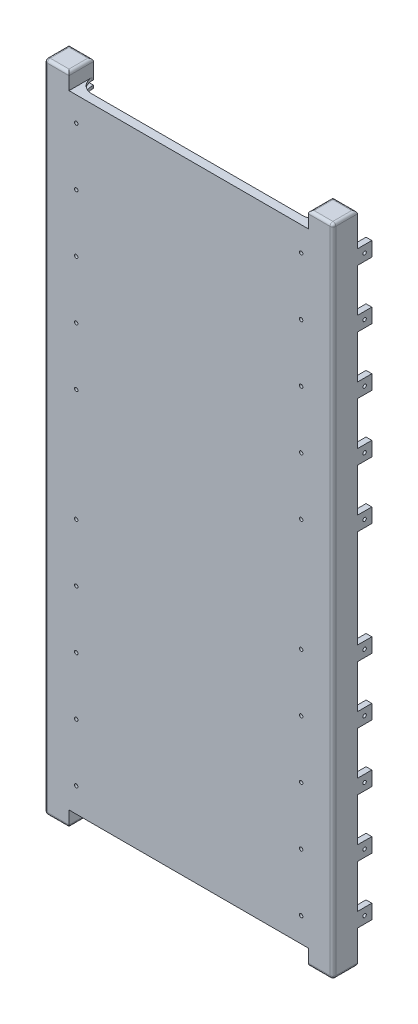
SolidWorks part; units mm, degrees
ref_plane "Front Plane" through (0, 0, 0) normal (0, 0, 1) x (1, 0, 0)
ref_plane "Top Plane" through (0, 0, 0) normal (0, 1, 0) x (1, 0, 0)
ref_plane "Right Plane" through (0, 0, 0) normal (1, 0, 0) x (0, 0, -1)
sketch "Sketch1" plane through (0, 0, 0) normal (0, 1, 0) x (1, 0, 0)
  line L1 (-3.25, -4.25) -> (4.25, -4.25)
  line L2 (-4.25, -3.25) -> (-4.25, 4.25)
  line L3 (-4.25, 4.25) -> (4.25, 4.25)
  line L4 (4.25, -4.25) -> (4.25, 4.25)
  line L5 (-4.25, -4.25) -> (4.25, 4.25) construction
  line L6 (-4.25, 4.25) -> (4.25, -4.25) construction
  arc A0 (-3.25, -4.25) -> (-4.25, -3.25) centre (-3.25, -3.25) cw
  point P0 (0, 0)
  dimension "D2" = 1
  dimension "D1" = 8.5
extrude "Boss-Extrude1" add sketch "Sketch1" along normal blind 227
ref_plane "Plane2" through (45.75, 0, 0) normal (-1, 0, 0) x (0, 0, 1)
ref_plane "Plane3" through (0, 113.5, 0) normal (0, 1, 0) x (1, 0, 0)
fillet "Fillet1" radius 1 10 edges at (0, 0, -4.25) (-4.25, 0, -0.5) (-3.9571, 0, 3.9571) (0.5, 0, 4.25) (4.25, 0, 0) (0.5, 227, 4.25) (-3.9571, 227, 3.9571) (-4.25, 227, -0.5) (0, 227, -4.25) (4.25, 227, 0)
ref_plane "Plane1" through (0, 0, 0) normal (-0.7071, 0, -0.7071) x (-0.7071, 0, 0.7071)
sketch "Sketch2" plane through (4.25, 0, 0) normal (1, 0, 0) x (0, 0, -1)
  line L0 (-4.25, 226) -> (-4.25, 1) construction
  line L1 (-4.25, 215.5) -> (-2.25, 215.5)
  line L2 (-4.25, 215.5) -> (-4.25, 210.5)
  line L3 (-4.25, 210.5) -> (-2.25, 210.5)
  line L4 (-2.25, 215.5) -> (-2.25, 210.5)
  line L5 (-3.25, 227) -> (3.25, 227) construction
  line L6 (-4.25, 195.5) -> (-2.25, 195.5)
  line L8 (-4.25, 195.5) -> (-4.25, 190.5)
  line L9 (-4.25, 190.5) -> (-2.25, 190.5)
  line L10 (-2.25, 195.5) -> (-2.25, 190.5)
  line L11 (-4.25, 175.5) -> (-2.25, 175.5)
  line L12 (-4.25, 175.5) -> (-4.25, 170.5)
  line L13 (-4.25, 170.5) -> (-2.25, 170.5)
  line L14 (-2.25, 175.5) -> (-2.25, 170.5)
  line L15 (-4.25, 155.5) -> (-2.25, 155.5)
  line L16 (-4.25, 155.5) -> (-4.25, 150.5)
  line L17 (-4.25, 150.5) -> (-2.25, 150.5)
  line L18 (-2.25, 155.5) -> (-2.25, 150.5)
  line L19 (-4.25, 135.5) -> (-2.25, 135.5)
  line L20 (-4.25, 135.5) -> (-4.25, 130.5)
  line L21 (-4.25, 130.5) -> (-2.25, 130.5)
  line L22 (-2.25, 135.5) -> (-2.25, 130.5)
  line L27 (-4.25, 120.5) -> (4.25, 120.5) construction
  line L28 (4.25, 226) -> (4.25, 1) construction
  line L29 (-4.25, 220.5) -> (4.25, 220.5) construction
  line L30 (-4.25, 113.5) -> (4.25, 113.5) construction
  line L35 (-2.25, 91.5) -> (-2.25, 96.5)
  line L36 (-4.25, 96.5) -> (-2.25, 96.5)
  line L37 (-4.25, 91.5) -> (-4.25, 96.5)
  line L38 (-4.25, 91.5) -> (-2.25, 91.5)
  line L39 (-2.25, 71.5) -> (-2.25, 76.5)
  line L40 (-4.25, 76.5) -> (-2.25, 76.5)
  line L41 (-4.25, 71.5) -> (-4.25, 76.5)
  line L42 (-4.25, 71.5) -> (-2.25, 71.5)
  line L43 (-2.25, 51.5) -> (-2.25, 56.5)
  line L44 (-4.25, 56.5) -> (-2.25, 56.5)
  line L45 (-4.25, 51.5) -> (-4.25, 56.5)
  line L46 (-4.25, 51.5) -> (-2.25, 51.5)
  line L47 (-2.25, 31.5) -> (-2.25, 36.5)
  line L48 (-4.25, 36.5) -> (-2.25, 36.5)
  line L49 (-4.25, 31.5) -> (-4.25, 36.5)
  line L50 (-4.25, 31.5) -> (-2.25, 31.5)
  line L51 (-2.25, 11.5) -> (-2.25, 16.5)
  line L52 (-4.25, 16.5) -> (-2.25, 16.5)
  line L53 (-4.25, 11.5) -> (-4.25, 16.5)
  line L54 (-4.25, 11.5) -> (-2.25, 11.5)
  line L55 (-4.25, 115.5) -> (-2.25, 115.5)
  line L56 (-4.25, 115.5) -> (-4.25, 110.5)
  line L57 (-2.25, 115.5) -> (-2.25, 110.5)
  line L58 (-4.25, 110.5) -> (-2.25, 110.5)
  dimension "D1" = 2
  dimension "D2" = 100
  dimension "D3" = 5
  dimension "D4" = 6
  dimension "D5" = 20
  dimension "D6" = 6.5
  dimension "D7" = 5
extrude "Boss-Extrude2" add sketch "Sketch2" along normal blind 5
sketch "Sketch13" plane through (4.25, 0, 0) normal (-1, 0, 0) x (0, 0, 1)
  line L1 (4.25, 220.5) -> (4.05, 220.5)
  line L2 (4.25, 220.5) -> (4.25, 6.5)
  line L3 (4.25, 6.5) -> (4.05, 6.5)
  line L4 (4.05, 220.5) -> (4.05, 6.5)
  line L6 (3.25, 227) -> (-3.25, 227) construction
  line L7 (-3.25, 0) -> (3.25, 0) construction
  dimension "D1" = 0.2
  dimension "D2" = 6.5
  dimension "D3" = 6.5
extrude "Boss-Extrude6" add sketch "Sketch13" along normal up to surface (41.5 mm away)
hole_wizard "#0-80 Tapped Hole1" positions "Sketch12" profile "Sketch11" tap size "#0-80" standard "ANSI Inch"
sketch "Sketch12" plane through (0, 0, 4.25) normal (0, 0, 1) x (1, 0, 0)
  line L0 (9.25, 215.5) -> (4.25, 215.5) construction
  line L2 (9.25, 215.5) -> (9.25, 210.5) construction
  line L5 (4.25, 113.5) -> (-3.25, 113.5) construction
  line L7 (-3.25, 226) -> (-3.25, 1) construction
  line L8 (4.25, 130.5) -> (4.25, 96.5) construction
  point P0 (6.75, 213)
  point P23 (6.75, 193)
  point P24 (6.75, 173)
  point P25 (6.75, 153)
  point P26 (6.75, 133)
  point P40 (6.75, 94)
  point P41 (6.75, 74)
  point P42 (6.75, 54)
  point P43 (6.75, 34)
  point P44 (6.75, 14)
  dimension "D1" = 2.5
  dimension "D2" = 2.5
  dimension "D4" = 20
  dimension "D3" = 5
sketch "Sketch11" plane through (6.75, 213, 4.25) normal (1, 0, 0) x (0, -1, 0)
  line L0 (0, 0) -> (0, 4.3584)
  line L1 (0, 4.3584) -> (0.5956, 4.0005)
  line L2 (0.5956, 4.0005) -> (0.5956, 0)
  line L5 (0.5956, 0) -> (0, 0)
  line L10 (0, 4.3584) -> (-0.5956, 4.0005) construction
  line L11 (0, -6.35) -> (0, 107.95) construction
  dimension "Tap Drill Dia." = 1.1913
  dimension "Tap Drill Depth" = 4.0005
  dimension "Drill Angle" = 118
cosmetic thread "Hole Thread1" parameters "D1"=2, "D2"=1.524
cosmetic thread "Hole Thread2" parameters "D1"=2, "D2"=1.524
cosmetic thread "Hole Thread11" parameters "D1"=2, "D2"=1.524
cosmetic thread "Hole Thread12" parameters "D1"=2, "D2"=1.524
cosmetic thread "Hole Thread13" parameters "D1"=2, "D2"=1.524
cosmetic thread "Hole Thread14" parameters "D1"=2, "D2"=1.524
cosmetic thread "Hole Thread15" parameters "D1"=2, "D2"=1.524
cosmetic thread "Hole Thread16" parameters "D1"=2, "D2"=1.524
cosmetic thread "Hole Thread17" parameters "D1"=2, "D2"=1.524
cosmetic thread "Hole Thread18" parameters "D1"=2, "D2"=1.524
fillet "Fillet2" radius 2.5 20 edges at (9.25, 215.5, 3.15) (9.25, 195.5, 3.15) (9.25, 175.5, 3.15) (9.25, 155.5, 3.15) (9.25, 135.5, 3.15) (9.25, 91.5, 3.15) (9.25, 71.5, 3.15) (9.25, 51.5, 3.15) (9.25, 31.5, 3.15) (9.25, 11.5, 3.15) (4.25, 215.5, 3.15) (4.25, 195.5, 3.15) (4.25, 175.5, 3.15) (4.25, 155.5, 3.15) (4.25, 135.5, 3.15) (4.25, 91.5, 3.15) (4.25, 71.5, 3.15) (4.25, 51.5, 3.15) (4.25, 11.5, 3.15) (4.25, 31.5, 3.15)
mirror "Mirror1" about plane through (0, 0, 0) normal (-0.7071, 0, -0.7071) of "#0-80 Tapped Hole1", "Boss-Extrude2"
sketch "Sketch3" plane through (0, 227, 0) normal (0, 1, 0) x (1, 0, 0)
  line L1 (-2.25, -2.25) -> (4.25, -2.25)
  line L2 (-2.25, -2.25) -> (-2.25, 4.25)
  line L3 (-2.25, 4.25) -> (4.25, 4.25)
  line L4 (4.25, -2.25) -> (4.25, 4.25)
  line L6 (4.25, -4.25) -> (-3.25, -4.25) construction
  line L7 (-4.25, -3.25) -> (-4.25, 4.25) construction
  dimension "D1" = 2
  dimension "D2" = 2
extrude "Cut-Extrude1" cut sketch "Sketch3" against normal offset from surface (214 mm away) 6.5 from offset 6.5 up to face at (0, 0, 0) offset against normal yes
mirror "Mirror7" about plane through (45.75, 0, 0) normal (-1, 0, 0) of "Fillet2", "Boss-Extrude1", "Fillet1", "Boss-Extrude2", "Boss-Extrude6", "#0-80 Tapped Hole1", "Mirror1", "Cut-Extrude1"
sketch "Sketch14" plane through (-2.25, 0, 0) normal (1, 0, 0) x (0, 0, -1)
  line L0 (-2.25, 6.5) -> (-2.25, 220.5) construction
  line L1 (-4.25, 8.1) -> (4.25, 8.1)
  line L2 (-4.25, 8.1) -> (-4.25, 9.1)
  line L3 (-4.25, 9.1) -> (4.25, 9.1)
  line L4 (4.25, 8.1) -> (4.25, 9.1)
  line L5 (4.25, 6.5) -> (4.25, 11.5) construction
  line L6 (4.25, 6.5) -> (-2.25, 6.5) construction
  line L7 (-4.25, 18.1) -> (4.25, 18.1)
  line L8 (-4.25, 6.5) -> (4.25, 6.5)
  line L9 (-4.25, 6.5) -> (-4.25, 5.5)
  line L10 (-4.25, 5.5) -> (4.25, 5.5)
  line L11 (4.25, 6.5) -> (4.25, 5.5)
  line L12 (-4.25, 18.1) -> (-4.25, 19.1)
  line L13 (-4.25, 19.1) -> (4.25, 19.1)
  line L14 (4.25, 18.1) -> (4.25, 19.1)
  line L15 (-4.25, 16.5) -> (4.25, 16.5)
  line L16 (-4.25, 16.5) -> (-4.25, 15.5)
  line L17 (-4.25, 15.5) -> (4.25, 15.5)
  line L18 (4.25, 16.5) -> (4.25, 15.5)
  line L19 (-4.25, 28.1) -> (4.25, 28.1)
  line L20 (-4.25, 28.1) -> (-4.25, 29.1)
  line L21 (-4.25, 29.1) -> (4.25, 29.1)
  line L22 (4.25, 28.1) -> (4.25, 29.1)
  line L23 (-4.25, 26.5) -> (4.25, 26.5)
  line L24 (-4.25, 26.5) -> (-4.25, 25.5)
  line L25 (-4.25, 25.5) -> (4.25, 25.5)
  line L26 (4.25, 26.5) -> (4.25, 25.5)
  line L27 (-4.25, 38.1) -> (4.25, 38.1)
  line L28 (-4.25, 38.1) -> (-4.25, 39.1)
  line L29 (-4.25, 39.1) -> (4.25, 39.1)
  line L30 (4.25, 38.1) -> (4.25, 39.1)
  line L31 (-4.25, 36.5) -> (4.25, 36.5)
  line L32 (-4.25, 36.5) -> (-4.25, 35.5)
  line L33 (-4.25, 35.5) -> (4.25, 35.5)
  line L34 (4.25, 36.5) -> (4.25, 35.5)
  line L35 (-4.25, 48.1) -> (4.25, 48.1)
  line L36 (-4.25, 48.1) -> (-4.25, 49.1)
  line L37 (-4.25, 49.1) -> (4.25, 49.1)
  line L38 (4.25, 48.1) -> (4.25, 49.1)
  line L39 (-4.25, 46.5) -> (4.25, 46.5)
  line L40 (-4.25, 46.5) -> (-4.25, 45.5)
  line L41 (-4.25, 45.5) -> (4.25, 45.5)
  line L42 (4.25, 46.5) -> (4.25, 45.5)
  line L43 (-4.25, 58.1) -> (4.25, 58.1)
  line L44 (-4.25, 58.1) -> (-4.25, 59.1)
  line L45 (-4.25, 59.1) -> (4.25, 59.1)
  line L46 (4.25, 58.1) -> (4.25, 59.1)
  line L47 (-4.25, 56.5) -> (4.25, 56.5)
  line L48 (-4.25, 56.5) -> (-4.25, 55.5)
  line L49 (-4.25, 55.5) -> (4.25, 55.5)
  line L50 (4.25, 56.5) -> (4.25, 55.5)
  line L51 (-4.25, 68.1) -> (4.25, 68.1)
  line L52 (-4.25, 68.1) -> (-4.25, 69.1)
  line L53 (-4.25, 69.1) -> (4.25, 69.1)
  line L54 (4.25, 68.1) -> (4.25, 69.1)
  line L55 (-4.25, 66.5) -> (4.25, 66.5)
  line L56 (-4.25, 66.5) -> (-4.25, 65.5)
  line L57 (-4.25, 65.5) -> (4.25, 65.5)
  line L58 (4.25, 66.5) -> (4.25, 65.5)
  line L59 (-4.25, 78.1) -> (4.25, 78.1)
  line L60 (-4.25, 78.1) -> (-4.25, 79.1)
  line L61 (-4.25, 79.1) -> (4.25, 79.1)
  line L62 (4.25, 78.1) -> (4.25, 79.1)
  line L63 (-4.25, 76.5) -> (4.25, 76.5)
  line L64 (-4.25, 76.5) -> (-4.25, 75.5)
  line L65 (-4.25, 75.5) -> (4.25, 75.5)
  line L66 (4.25, 76.5) -> (4.25, 75.5)
  line L67 (-4.25, 88.1) -> (4.25, 88.1)
  line L68 (-4.25, 88.1) -> (-4.25, 89.1)
  line L69 (-4.25, 89.1) -> (4.25, 89.1)
  line L70 (4.25, 88.1) -> (4.25, 89.1)
  line L71 (-4.25, 86.5) -> (4.25, 86.5)
  line L72 (-4.25, 86.5) -> (-4.25, 85.5)
  line L73 (-4.25, 85.5) -> (4.25, 85.5)
  line L74 (4.25, 86.5) -> (4.25, 85.5)
  line L75 (-4.25, 98.1) -> (4.25, 98.1)
  line L76 (-4.25, 98.1) -> (-4.25, 99.1)
  line L77 (-4.25, 99.1) -> (4.25, 99.1)
  line L78 (4.25, 98.1) -> (4.25, 99.1)
  line L79 (-4.25, 96.5) -> (4.25, 96.5)
  line L80 (-4.25, 96.5) -> (-4.25, 95.5)
  line L81 (-4.25, 95.5) -> (4.25, 95.5)
  line L82 (4.25, 96.5) -> (4.25, 95.5)
  line L83 (-4.25, 108.1) -> (4.25, 108.1)
  line L84 (-4.25, 108.1) -> (-4.25, 109.1)
  line L85 (-4.25, 109.1) -> (4.25, 109.1)
  line L86 (4.25, 108.1) -> (4.25, 109.1)
  line L87 (-4.25, 106.5) -> (4.25, 106.5)
  line L88 (-4.25, 106.5) -> (-4.25, 105.5)
  line L89 (-4.25, 105.5) -> (4.25, 105.5)
  line L90 (4.25, 106.5) -> (4.25, 105.5)
  line L91 (4.25, 96.5) -> (4.25, 130.5) construction
  line L92 (4.25, 113.5) -> (-2.25, 113.5) construction
  line L93 (4.25, 120.5) -> (4.25, 121.5)
  line L94 (-4.25, 121.5) -> (4.25, 121.5)
  line L95 (-4.25, 120.5) -> (-4.25, 121.5)
  line L96 (-4.25, 120.5) -> (4.25, 120.5)
  line L97 (4.25, 118.9) -> (4.25, 117.9)
  line L98 (-4.25, 117.9) -> (4.25, 117.9)
  line L99 (-4.25, 118.9) -> (-4.25, 117.9)
  line L100 (-4.25, 118.9) -> (4.25, 118.9)
  line L101 (4.25, 130.5) -> (4.25, 131.5)
  line L102 (-4.25, 131.5) -> (4.25, 131.5)
  line L103 (-4.25, 130.5) -> (-4.25, 131.5)
  line L104 (-4.25, 130.5) -> (4.25, 130.5)
  line L105 (4.25, 128.9) -> (4.25, 127.9)
  line L106 (-4.25, 127.9) -> (4.25, 127.9)
  line L107 (-4.25, 128.9) -> (-4.25, 127.9)
  line L108 (-4.25, 128.9) -> (4.25, 128.9)
  line L109 (4.25, 140.5) -> (4.25, 141.5)
  line L110 (-4.25, 141.5) -> (4.25, 141.5)
  line L111 (-4.25, 140.5) -> (-4.25, 141.5)
  line L112 (-4.25, 140.5) -> (4.25, 140.5)
  line L113 (4.25, 138.9) -> (4.25, 137.9)
  line L114 (-4.25, 137.9) -> (4.25, 137.9)
  line L115 (-4.25, 138.9) -> (-4.25, 137.9)
  line L116 (-4.25, 138.9) -> (4.25, 138.9)
  line L117 (4.25, 150.5) -> (4.25, 151.5)
  line L118 (-4.25, 151.5) -> (4.25, 151.5)
  line L119 (-4.25, 150.5) -> (-4.25, 151.5)
  line L120 (-4.25, 150.5) -> (4.25, 150.5)
  line L121 (4.25, 148.9) -> (4.25, 147.9)
  line L122 (-4.25, 147.9) -> (4.25, 147.9)
  line L123 (-4.25, 148.9) -> (-4.25, 147.9)
  line L124 (-4.25, 148.9) -> (4.25, 148.9)
  line L125 (4.25, 160.5) -> (4.25, 161.5)
  line L126 (-4.25, 161.5) -> (4.25, 161.5)
  line L127 (-4.25, 160.5) -> (-4.25, 161.5)
  line L128 (-4.25, 160.5) -> (4.25, 160.5)
  line L129 (4.25, 158.9) -> (4.25, 157.9)
  line L130 (-4.25, 157.9) -> (4.25, 157.9)
  line L131 (-4.25, 158.9) -> (-4.25, 157.9)
  line L132 (-4.25, 158.9) -> (4.25, 158.9)
  line L133 (4.25, 170.5) -> (4.25, 171.5)
  line L134 (-4.25, 171.5) -> (4.25, 171.5)
  line L135 (-4.25, 170.5) -> (-4.25, 171.5)
  line L136 (-4.25, 170.5) -> (4.25, 170.5)
  line L137 (4.25, 168.9) -> (4.25, 167.9)
  line L138 (-4.25, 167.9) -> (4.25, 167.9)
  line L139 (-4.25, 168.9) -> (-4.25, 167.9)
  line L140 (-4.25, 168.9) -> (4.25, 168.9)
  line L141 (4.25, 180.5) -> (4.25, 181.5)
  line L142 (-4.25, 181.5) -> (4.25, 181.5)
  line L143 (-4.25, 180.5) -> (-4.25, 181.5)
  line L144 (-4.25, 180.5) -> (4.25, 180.5)
  line L145 (4.25, 178.9) -> (4.25, 177.9)
  line L146 (-4.25, 177.9) -> (4.25, 177.9)
  line L147 (-4.25, 178.9) -> (-4.25, 177.9)
  line L148 (-4.25, 178.9) -> (4.25, 178.9)
  line L149 (4.25, 190.5) -> (4.25, 191.5)
  line L150 (-4.25, 191.5) -> (4.25, 191.5)
  line L151 (-4.25, 190.5) -> (-4.25, 191.5)
  line L152 (-4.25, 190.5) -> (4.25, 190.5)
  line L153 (4.25, 188.9) -> (4.25, 187.9)
  line L154 (-4.25, 187.9) -> (4.25, 187.9)
  line L155 (-4.25, 188.9) -> (-4.25, 187.9)
  line L156 (-4.25, 188.9) -> (4.25, 188.9)
  line L157 (4.25, 200.5) -> (4.25, 201.5)
  line L158 (-4.25, 201.5) -> (4.25, 201.5)
  line L159 (-4.25, 200.5) -> (-4.25, 201.5)
  line L160 (-4.25, 200.5) -> (4.25, 200.5)
  line L161 (4.25, 198.9) -> (4.25, 197.9)
  line L162 (-4.25, 197.9) -> (4.25, 197.9)
  line L163 (-4.25, 198.9) -> (-4.25, 197.9)
  line L164 (-4.25, 198.9) -> (4.25, 198.9)
  line L165 (4.25, 210.5) -> (4.25, 211.5)
  line L166 (-4.25, 211.5) -> (4.25, 211.5)
  line L167 (-4.25, 210.5) -> (-4.25, 211.5)
  line L168 (-4.25, 210.5) -> (4.25, 210.5)
  line L169 (4.25, 208.9) -> (4.25, 207.9)
  line L170 (-4.25, 207.9) -> (4.25, 207.9)
  line L171 (-4.25, 208.9) -> (-4.25, 207.9)
  line L172 (4.25, 220.5) -> (4.25, 221.5)
  line L173 (-4.25, 221.5) -> (4.25, 221.5)
  line L174 (-4.25, 220.5) -> (-4.25, 221.5)
  line L175 (-4.25, 220.5) -> (4.25, 220.5)
  line L176 (-4.25, 208.9) -> (4.25, 208.9)
  line L177 (4.25, 218.9) -> (4.25, 217.9)
  line L178 (-4.25, 217.9) -> (4.25, 217.9)
  line L179 (-4.25, 218.9) -> (-4.25, 217.9)
  line L180 (-4.25, 218.9) -> (4.25, 218.9)
  dimension "D1" = 1
  dimension "D2" = 1.6
  dimension "D4" = 10
  dimension "D5" = 8.5
  dimension "D3" = 11
extrude "Boss-Extrude7" add sketch "Sketch14" along normal up to surface (96 mm away)
sketch "Sketch15" plane through (0, 5.5, 0) normal (0, -1, 0) x (1, 0, 0)
  line L0 (4.25, -4.25) -> (4.25, -3.75)
  line L2 (4.25, -4.25) -> (87.25, -4.25)
  line L3 (87.25, -4.25) -> (87.25, -3.75)
  line L4 (87.25, -4.25) -> (87.25, 4.25) construction
  line L5 (4.25, 4.25) -> (4.25, -4.25) construction
  line L6 (9.25, 1.25) -> (82.25, 1.25)
  line L7 (87.25, 4.25) -> (4.25, 4.25) construction
  arc A0 (4.25, -3.75) -> (9.25, 1.25) centre (9.25, -3.75) cw
  arc A1 (87.25, -3.75) -> (82.25, 1.25) centre (82.25, -3.75) ccw
  point P14 (4.25, 1.25)
  point P17 (87.25, 1.25)
  dimension "D2" = 5
  dimension "D1" = 3
extrude "Cut-Extrude2" cut sketch "Sketch15" against normal through all
